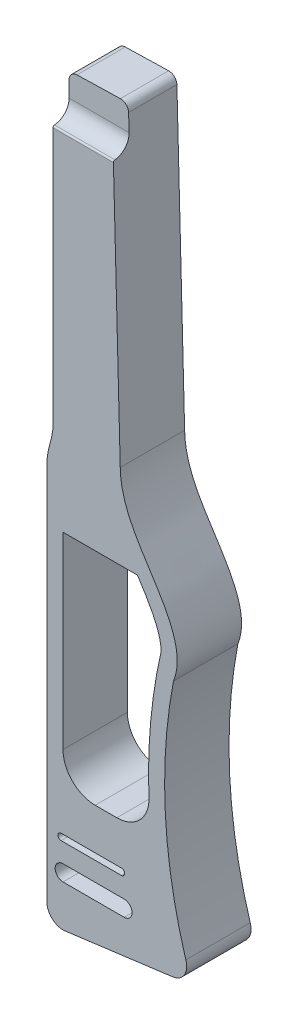
SolidWorks part; units mm, degrees
ref_plane "Front Plane" through (0, 0, 0) normal (0, 0, 1) x (1, 0, 0)
ref_plane "Top Plane" through (0, 0, 0) normal (0, 1, 0) x (1, 0, 0)
ref_plane "Right Plane" through (0, 0, 0) normal (1, 0, 0) x (0, 0, -1)
sketch "Sketch1" plane through (0, 0, 0) normal (0, 0, 1) x (1, 0, 0)
  line L0 (276.2916, 510.6659) -> (276.2916, 160.6659) construction
  line L1 (260.1972, 533.779) -> (287.1579, 534.4514)
  line L2 (292.2808, 529.5836) -> (298.3219, 298.3099)
  line L3 (298.3219, 298.3099) -> (255.3219, 298.3099)
  line L4 (255.3219, 298.3099) -> (255.3219, 528.7806)
  line L5 (255.3219, 508.8699) -> (292.8219, 508.8699) construction
  line L6 (251.5219, 199.0934) -> (345.6901, 199.0934) construction
  line L7 (251.5219, 107.6874) -> (251.5219, 107.3771)
  line L8 (251.5219, 107.9751) -> (251.5219, 107.3771)
  line L9 (240.6841, 238.5178) -> (380.6841, 238.5178) construction
  line L10 (276.7839, 81.3421) -> (329.6613, 88.2445)
  line L11 (251.5219, 324.5663) -> (251.5219, 112.4943)
  line L12 (251.5219, 112.4943) -> (251.5219, 89.4347)
  line L13 (262.8163, 79.5188) -> (276.7839, 81.3421)
  arc A0 (251.5219, 324.5663) -> (253.0083, 335.3692) centre (291.5219, 324.5663) cw
  arc A1 (329.6613, 88.2445) -> (337.8127, 101.4433) centre (328.3669, 98.1604) ccw
  arc A4 (337.8127, 101.4433) -> (330.1566, 247.6257) centre (628.9976, 189.9854) cw
  arc A5 (251.5219, 89.4347) -> (262.8163, 79.5188) centre (261.5219, 89.4347) ccw
  arc A7 (287.1579, 534.4514) -> (292.2808, 529.5836) centre (287.2825, 529.453) cw
  arc A8 (260.1972, 533.779) -> (255.3219, 528.7806) centre (260.3219, 528.7806) ccw
  spline S0 degree 3 poles (330.1566, 247.6257) (336.0067, 262.2774) (320.7677, 296.8043) (297.4139, 323.5094) (297.0755, 346.0277) knots 0 0 0 0 0.411549 1 1 1 1
  spline S1 degree 3 poles (255.3219, 346.0277) (254.758, 342.4104) (253.9868, 338.8575) (253.0083, 335.3692) knots 0 0 0 0 0.135222 0.135222 0.135222 0.135222
  point P8 (255.3219, 346.0277)
  point P19 (297.7108, 321.7063)
  point P32 (275.6533, 157.9176)
  dimension "D2" = 40
  dimension "D3" = 210.56
  dimension "D4" = 5
  dimension "D8" = 10
  dimension "D10" = 10
  dimension "D1" = 350
  dimension "D5" = 37.5
  dimension "D6" = 43
  dimension "D7" = 140
extrude "Boss-Extrude3" add sketch "Sketch1" along normal blind 40 contours L1 A8 L4 L3 L2 A7 | L8 L2 L3 L4 region at (275.3339, 413.0488, 0) region at (289.8275, 192.4047, 0)
sketch "Sketch3" plane through (0, 0, 40) normal (0, 0, 1) x (1, 0, 0)
  line L0 (255.3219, 508.8699) -> (292.8219, 508.8699) construction
  line L1 (255.3219, 508.8699) -> (292.8219, 508.8699)
  line L2 (292.2808, 529.5836) -> (298.3219, 298.3099) construction
  line L3 (260.1972, 533.779) -> (287.1579, 534.4514) construction
  line L4 (255.3219, 298.3099) -> (255.3219, 528.7806) construction
  line L5 (292.2808, 529.5836) -> (292.8219, 508.8699)
  line L6 (260.1972, 533.779) -> (287.1579, 534.4514)
  line L7 (255.3219, 508.8699) -> (255.3219, 528.7806)
  line L8 (260.3219, 128.8699) -> (297.8219, 128.8699) construction
  line L9 (260.3219, 126.8699) -> (297.8219, 126.8699)
  line L10 (260.3219, 130.8699) -> (297.8219, 130.8699)
  arc A0 (292.2808, 529.5836) -> (287.1579, 534.4514) centre (287.2825, 529.453) ccw construction
  arc A1 (260.1972, 533.779) -> (255.3219, 528.7806) centre (260.3219, 528.7806) ccw construction
  arc A2 (292.2808, 529.5836) -> (287.1579, 534.4514) centre (287.2825, 529.453) ccw
  arc A3 (260.1972, 533.779) -> (255.3219, 528.7806) centre (260.3219, 528.7806) ccw
  arc A4 (260.3219, 126.8699) -> (260.3219, 130.8699) centre (260.3219, 128.8699) cw
  arc A5 (297.8219, 126.8699) -> (297.8219, 130.8699) centre (297.8219, 128.8699) ccw
  dimension "D3" = 380
  dimension "D4" = 37.5
  dimension "D1" = 2
  dimension "D2" = 2
extrude "Cut-Extrude1" cut sketch "Sketch3" against normal blind 10
fillet "Fillet3" radius 10 1 edges at (274.0719, 508.8699, 30) type face fillet first side face at (273.8486, 524.3977, 30) second side face at (274.0719, 508.8699, 35)
fillet "Fillet4" radius 1 1 edges at (274.0719, 508.8699, 40) type face fillet first side face at (279.0719, 128.8699, 40) second side face at (274.0201, 512.8344, 33.9645)
sketch "Sketch6" plane through (0, 0, 40) normal (0, 0, 1) x (1, 0, 0)
  line L0 (260.3219, 128.8699) -> (297.8219, 128.8699) construction
  line L1 (260.3219, 126.8699) -> (297.8219, 126.8699) construction
  line L2 (260.3219, 130.8699) -> (297.8219, 130.8699) construction
  line L3 (260.3219, 128.8699) -> (297.8219, 128.8699) construction
  line L4 (260.3219, 126.8699) -> (297.8219, 126.8699)
  line L5 (260.3219, 130.8699) -> (297.8219, 130.8699)
  arc A0 (260.3219, 130.8699) -> (260.3219, 126.8699) centre (260.3219, 128.8699) ccw construction
  arc A1 (297.8219, 126.8699) -> (297.8219, 130.8699) centre (297.8219, 128.8699) ccw construction
  arc A2 (260.3219, 130.8699) -> (260.3219, 126.8699) centre (260.3219, 128.8699) ccw
  arc A3 (297.8219, 126.8699) -> (297.8219, 130.8699) centre (297.8219, 128.8699) ccw
sketch "Sketch7" plane through (0, 0, 0) normal (0, 0, 1) x (1, 0, 0)
  line L1 (251.5219, 324.5663) -> (251.5219, 89.4347) construction
  line L2 (261.5219, 110.1299) -> (299.5208, 110.1299) construction
  line L3 (251.5219, 324.5663) -> (251.5219, 146.4933)
  line L4 (261.5219, 115.0244) -> (299.5208, 115.0244)
  line L5 (297.0755, 346.0277) -> (292.8468, 507.9155)
  line L6 (292.8468, 507.9155) -> (255.3219, 507.9155)
  line L7 (255.3219, 507.9155) -> (255.3219, 346.0277)
  line L8 (251.5219, 324.5663) -> (251.5219, 89.4347)
  line L9 (262.8163, 79.5188) -> (329.6613, 88.2445)
  line L10 (297.0755, 346.0277) -> (292.8468, 507.9155)
  line L11 (292.8468, 507.9155) -> (255.3219, 507.9155)
  line L12 (255.3219, 507.9155) -> (255.3219, 346.0277)
  line L13 (251.5219, 324.5663) -> (251.5219, 146.4933)
  line L14 (261.5219, 105.2354) -> (299.5208, 105.2354)
  line L15 (261.5219, 293.4111) -> (307.7839, 293.4111)
  line L16 (261.5219, 293.4111) -> (261.5219, 176.4933)
  line L17 (281.5219, 156.4933) -> (294.9209, 156.4933)
  line L18 (261.5219, 156.4933) -> (316.4378, 156.4933) construction
  line L19 (261.5219, 324.5663) -> (261.5219, 156.4933) construction
  line L20 (251.5219, 146.4933) -> (327.7721, 146.4933) construction
  arc A0 (329.6613, 88.2445) -> (337.8127, 101.4433) centre (328.3669, 98.1604) ccw construction
  arc A3 (329.6613, 88.2445) -> (337.8127, 101.4433) centre (328.3669, 98.1604) ccw
  arc A5 (253.0083, 335.3692) -> (251.5219, 324.5663) centre (291.5219, 324.5663) ccw
  arc A6 (251.5219, 89.4347) -> (262.8163, 79.5188) centre (261.5219, 89.4347) ccw
  arc A7 (251.5219, 89.4347) -> (262.8163, 79.5188) centre (261.5219, 89.4347) ccw
  arc A8 (329.6613, 88.2445) -> (337.8127, 101.4433) centre (328.3669, 98.1604) ccw
  arc A9 (330.1566, 247.6257) -> (337.8127, 101.4433) centre (628.9976, 189.9854) ccw
  arc A10 (253.0083, 335.3692) -> (251.5219, 324.5663) centre (291.5219, 324.5663) ccw
  arc A11 (261.5219, 115.0244) -> (261.5219, 105.2354) centre (261.5219, 110.1299) ccw
  arc A12 (299.5208, 105.2354) -> (299.5208, 115.0244) centre (299.5208, 110.1299) ccw
  arc A13 (329.6613, 88.2445) -> (337.8127, 101.4433) centre (328.3669, 98.1604) ccw
  arc A14 (332.4349, 258.3878) -> (327.7721, 146.4933) centre (628.9976, 189.9854) ccw
  arc A16 (334.6794, 112.4926) -> (337.8127, 101.4433) centre (628.9976, 189.9854) ccw
  arc A18 (322.6907, 260.6353) -> (314.9046, 177.3003) centre (628.9976, 189.9854) ccw
  arc A19 (322.6907, 260.6353) -> (316.4378, 156.4933) centre (628.9976, 189.9854) ccw construction
  arc A20 (294.9209, 156.4933) -> (314.9046, 177.3003) centre (294.9209, 176.4933) ccw
  arc A21 (261.5219, 176.4933) -> (281.5219, 156.4933) centre (281.5219, 176.4933) ccw
  arc A22 (262.6367, 332.6685) -> (261.5219, 324.5663) centre (291.5219, 324.5663) ccw construction
  parabola Q1 (255.3219, 346.0277) -> (253.0083, 335.3692) focus (209.0149, 346.3764) apex (252.2805, 332.9088)
  parabola Q2 (255.3219, 346.0277) -> (253.0083, 335.3692) focus (209.0149, 346.3764) apex (252.2805, 332.9088)
  spline S0 degree 1 poles (265.2025, 344.4874) (262.6367, 332.6685) knots 0 0 1 1 construction
  spline S1 degree 3 poles (-2660.7785, 112.6849) (363.4058, 65.704) (382.2424, 378.699) (109.8402, 410.9756) (2765.8234, 2041.7604) knots -2.265378 -2.265378 -2.265378 -2.265378 0.411549 3.725412 3.725412 3.725412 3.725412 only from (330.1566, 247.6257) to (297.0755, 346.0277)
  spline S2 degree 3 poles (330.1566, 247.6257) (336.0067, 262.2774) (320.7677, 296.8043) (297.4139, 323.5094) (297.0755, 346.0277) knots 0 0 0 0 0.411549 1 1 1 1
  spline S3 degree 3 poles (265.2025, 344.4874) (264.8913, 342.4911) (264.1501, 338.5088) (263.1803, 334.6065) (262.6367, 332.6685) knots 0.499501 0.499501 0.499501 0.499501 0.499703 0.499905 0.499905 0.499905 0.499905
  spline S4 degree 1 poles (320.8695, 251.3339) (287.0766, 345.8774) knots 0 0 1 1 construction
  spline S5 degree 3 poles (320.8695, 251.3339) (321.0228, 251.7177) (321.3123, 252.5032) (321.7813, 254.0271) (322.1981, 255.9127) (322.4513, 258.1673) (322.4855, 261.2168) (321.9775, 265.1788) (320.5161, 270.2431) (318.2826, 275.5543) (315.4254, 281.0218) (312.1623, 286.5288) (309.2631, 291.1136) (305.6507, 296.7263) (300.7005, 304.4068) (295.4041, 313.6616) (291.5072, 322.6551) (289.1563, 329.8664) (287.8271, 336.3034) (287.2294, 341.6838) (287.0975, 344.4877) (287.0766, 345.8774) knots 0 0 0 0 0.015625 0.03125 0.0625 0.09375 0.125 0.1875 0.25 0.3125 0.375 0.4375 0.498594 0.529844 0.625 0.75 0.8125 0.875 0.9375 0.96875 1 1 1 1
  point P47 (280.5213, 110.1299)
  dimension "D3" = 20
  dimension "D1" = 0
  dimension "D2" = 10
extrude "Cut-Extrude3" cut sketch "Sketch7" along normal through all contours L14 A12 L4 A11 | L16 A21 L17 A20 A18 S5 region at (280.5213, 110.1299, 0) region at (289.1435, 227.1433, 0)
sketch "Sketch8" plane through (363.4128, 308.4537, -17.1556) normal (0, 0, 1) x (1, 0, 0)
  line L0 (-101.8909, -13.6499) -> (-65.0518, -13.1689)
  line L1 (-101.8909, -15.0425) -> (-101.8909, -131.9604) construction
  line L2 (-108.0482, -13.7303) -> (-65.0518, -13.1689) construction
  line L3 (-65.0518, -13.1689) -> (-55.6289, -15.0425)
